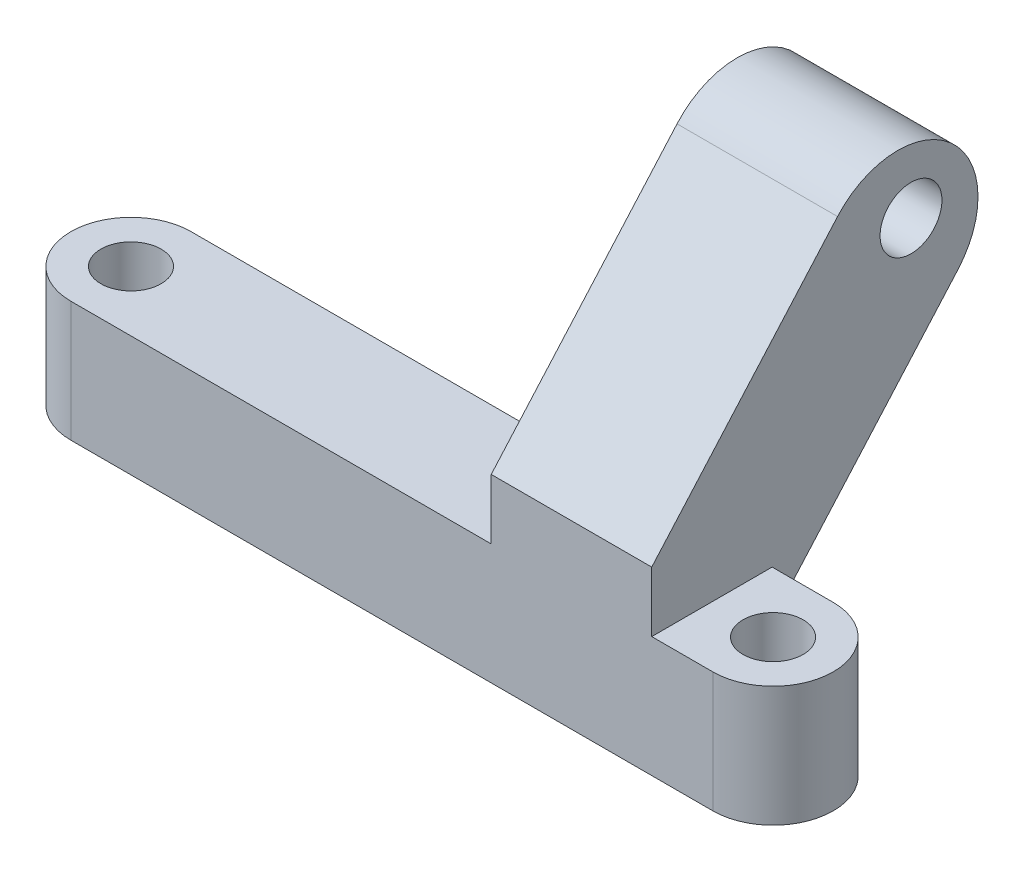
SolidWorks part; units mm, degrees
ref_plane "前基準面" through (0, 0, 0) normal (0, 0, 1) x (1, 0, 0)
ref_plane "上基準面" through (0, 0, 0) normal (0, 1, 0) x (1, 0, 0)
ref_plane "右基準面" through (0, 0, 0) normal (1, 0, 0) x (0, 0, -1)
sketch "草圖1" plane through (0, 0, 0) normal (0, 1, 0) x (1, 0, 0)
  line L0 (-38.677, 0) -> (-6.677, 0) construction
  line L1 (-38.677, 3) -> (-6.677, 3)
  line L2 (-38.677, -3) -> (-6.677, -3)
  line L4 (-17.7228, 3) -> (-9.7228, 3)
  line L5 (-17.7228, 3) -> (-17.7228, -3)
  line L6 (-17.7228, -3) -> (-9.7228, -3)
  line L7 (-9.7228, 3) -> (-9.7228, -3)
  arc A0 (-38.677, 3) -> (-38.677, -3) centre (-38.677, 0) ccw
  arc A1 (-6.677, -3) -> (-6.677, 3) centre (-6.677, 0) ccw
  circle A2 centre (-6.677, 0) radius 1.5
  circle A3 centre (-38.677, 0) radius 1.5
  point P3 (-22.677, 0)
  dimension "D1" = 32
  dimension "D2" = 8
  dimension "D4" = 3
  dimension "D3" = 6
extrude "填料-伸長2" add sketch "草圖1" against normal blind 6 contours A3 L5 L1 A0 L2 | L5 L0 L7 L1 | L0 L5 L2 L7 | L2 A1 L1 L7 A2 region at (-17.9697, 0, 1.5) region at (-13.7228, 0, -1.5) region at (-13.7228, 0, 1.5) region at (-9.6376, 0, -1.5)
extrude "填料-伸長3" add sketch "草圖1<4>" along normal blind 3 contours L0 L5 L2 L7 | L5 L0 L7 L1 region at (-13.7228, 0, -1.5) region at (-13.7228, 0, 1.5)
sketch "草圖1<4>" plane through (0, 0, 0) normal (0, 1, 0) x (1, 0, 0) same geometry as "草圖1"
sketch "草圖3" plane through (-9.7228, 0, 0) normal (1, 0, 0) x (0, 0, -1)
  line L0 (-3, 3) -> (-3, 0) construction
  line L2 (-3, 2.6558) -> (-3, 0)
  line L3 (9.2601, 10.8542) -> (0, 0.3542) construction
  line L4 (3, -6) -> (3, 0) construction
  line L5 (12.2601, 8.2085) -> (6.2601, 13.5)
  line L6 (12.2601, 8.2085) -> (3, -2.2915)
  line L7 (6.2601, 13.5) -> (-3, 3)
  line L8 (3, -2.2915) -> (-3, 3)
  line L9 (12.2601, 8.2085) -> (3, -2.2915)
  line L10 (6.2601, 13.5) -> (-3, 3)
  arc A0 (12.2601, 8.2085) -> (6.2601, 13.5) centre (9.2601, 10.8542) ccw
  arc A1 (-3, 3) -> (3, -2.2915) centre (0, 0.3542) ccw
  point P15 (4.6301, 5.6042)
  dimension "D1" = 8
  dimension "D2" = 14
extrude "填料-伸長28" add sketch "草圖3" against normal blind 8 contours L5 A0 | L5 L7 L8 L6 region at (-9.7228, 12.1275, -10.383)
sketch "草圖8" plane through (-9.7228, 0, 0) normal (1, 0, 0) x (0, 0, -1)
  line L0 (6.2601, 13.5) -> (-3, 3) construction
  circle A0 centre (9.9216, 11.6042) radius 1.5424
  arc A1 (12.2601, 8.2085) -> (6.2601, 13.5) centre (9.2601, 10.8542) ccw construction
  point P4 (11.9059, 13.8542)
  dimension "D1" = 4
  dimension "D2" = 3
extrude "除料-伸長2" cut sketch "草圖8" against normal blind 12 contours A0
